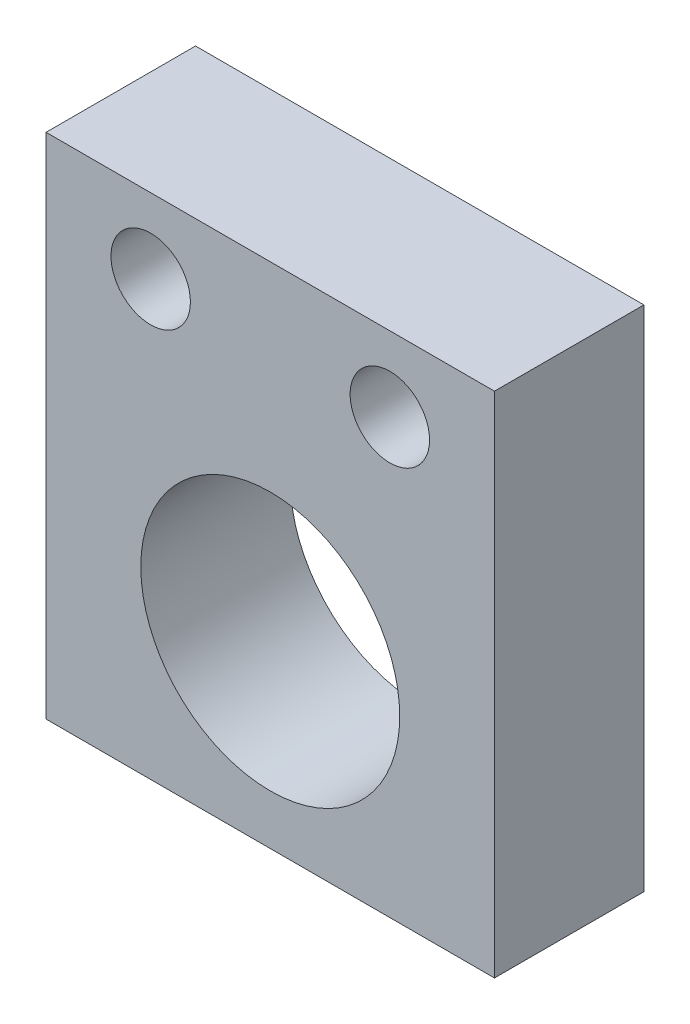
SolidWorks part; units mm, degrees
material "6063-T5"
ref_plane "Front Plane" through (0, 0, 0) normal (0, 0, 1) x (1, 0, 0)
ref_plane "Top Plane" through (0, 0, 0) normal (0, 1, 0) x (1, 0, 0)
ref_plane "Right Plane" through (0, 0, 0) normal (1, 0, 0) x (0, 0, -1)
sketch "Sketch1" plane through (0, 0, 0) normal (0, 0, 1) x (1, 0, 0)
  line L1 (0, 0) -> (38.1, 0)
  line L2 (0, 0) -> (0, 43.18)
  line L3 (0, 43.18) -> (38.1, 43.18)
  line L4 (38.1, 0) -> (38.1, 43.18)
  dimension "D1" = 38.1
  dimension "D2" = 43.18
extrude "Boss-Extrude1" add sketch "Sketch1" against normal blind 12.7
sketch "Sketch3" plane through (0, 0, 0) normal (0, 0, 1) x (1, 0, 0)
  line L0 (19.05, -987.2485) -> (19.05, 49012.7515) construction
  line L1 (0, 43.18) -> (0, 0) construction
  line L2 (38.1, 0) -> (38.1, 43.18) construction
  line L3 (38.1, 43.18) -> (0, 43.18) construction
  circle A0 centre (19.05, 15.24) radius 11
  dimension "D1" = 27.94
extrude "Cut-Extrude1" cut sketch "Sketch3" against normal through all contours A0
sketch "Sketch5" plane through (0, 0, 0) normal (0, 0, 1) x (1, 0, 0)
  line L0 (19.05, -968.1712) -> (19.05, 49031.8288) construction
  line L1 (0, 43.18) -> (0, 0) construction
  line L2 (38.1, 0) -> (38.1, 43.18) construction
  line L3 (38.1, 43.18) -> (0, 43.18) construction
  point P6 (8.89, 36.83)
  point P7 (29.21, 36.83)
  dimension "D1" = 20.32
  dimension "D2" = 6.35
hole_wizard "17/64 (0.26563) Diameter Hole1" positions "3DSketch2" profile "Sketch7" hole size "17/64" standard "ANSI Inch" end condition through all
sketch3d "3DSketch2"
  point P0 (29.21, 36.83, 0)
  point P3 (8.89, 36.83, 0)
sketch "Sketch7" plane through (29.21, 36.83, 0) normal (1, 0, 0) x (0, -1, 0)
  line L0 (0, 0) -> (0, 12.7)
  line L1 (0, 12.7) -> (3.3735, 12.7)
  line L2 (3.3735, 12.7) -> (3.3735, 0)
  line L5 (3.3735, 0) -> (0, 0)
  line L11 (0, -6.35) -> (0, 107.95) construction
  dimension "Thru Hole Dia." = 6.747
  dimension "Thru Hole Depth" = 12.7
sketch "Sketch11" plane through (0, 0, 0) normal (-1, 0, 0) x (0, 0, 1)
  line L0 (-6.35, -976.0873) -> (-6.35, 49023.9127) construction
  line L1 (-12.7, 43.18) -> (-12.7, 0) construction
  line L2 (0, -200968.1712) -> (0, 249031.8288) construction
  line L3 (-12.7, 43.18) -> (0, 43.18) construction
  point P6 (-6.35, 27.94)
  dimension "D1" = 15.24
hole_wizard "1/4-20 Tapped Hole2" positions "3DSketch4" profile "Sketch12" tap size "1/4-20" standard "ANSI Inch"
sketch3d "3DSketch4"
  point P0 (0, 27.94, -6.35)
sketch "Sketch12" plane through (0, 27.94, -6.35) normal (0, 1, 0) x (0, 0, 1)
  line L0 (0, 0) -> (0, 14.2338)
  line L1 (0, 14.2338) -> (2.5527, 12.7)
  line L2 (2.5527, 12.7) -> (2.5527, 0)
  line L5 (2.5527, 0) -> (0, 0)
  line L10 (0, 14.2338) -> (-2.5527, 12.7) construction
  line L11 (0, -6.35) -> (0, 107.95) construction
  dimension "Tap Drill Dia." = 5.1054
  dimension "Tap Drill Depth" = 12.7
  dimension "Drill Angle" = 118
cosmetic thread "Hole Thread2" parameters "D1"=10.16, "D2"=6.35
